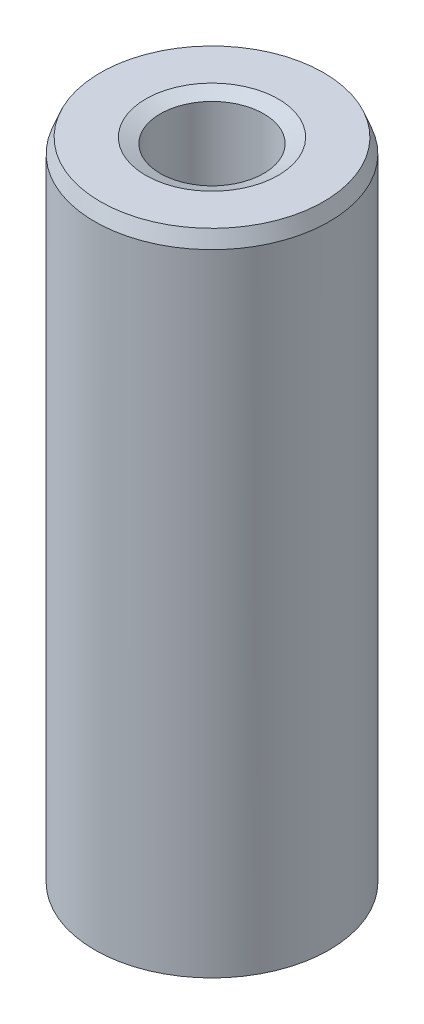
SolidWorks part; units mm, degrees
ref_plane "Front Plane" through (0, 0, 0) normal (0, 0, 1) x (1, 0, 0)
ref_plane "Top Plane" through (0, 0, 0) normal (0, 1, 0) x (1, 0, 0)
ref_plane "Right Plane" through (0, 0, 0) normal (1, 0, 0) x (0, 0, -1)
sketch "Sketch1" plane through (0, 0, 0) normal (0, 1, 0) x (1, 0, 0)
  circle A0 centre (0, 0) radius 10
  dimension "SLEEVE_OD" = 20
extrude "Boss-Extrude1" add sketch "Sketch1" along normal blind 55.4875
sketch "Sketch2" plane through (0, 0, 0) normal (0, 1, 0) x (1, 0, 0)
  circle A0 centre (0, 0) radius 4.4104
  dimension "BORE_D" = 8.8209
extrude "Cut-Extrude1" cut sketch "Sketch2" along normal through all
chamfer "Chamfer1" distance 1.2376 angle 21.133 4 edges at (0, 55.4875, 4.4104) (0, 0, 4.4104) (0, 0, 10) (0, 55.4875, 10) first distance on face at (0, 55.4875, 4.4104) first distance on face at (0, 0, 4.4104) first distance on face at (0, 55.4875, 10)
